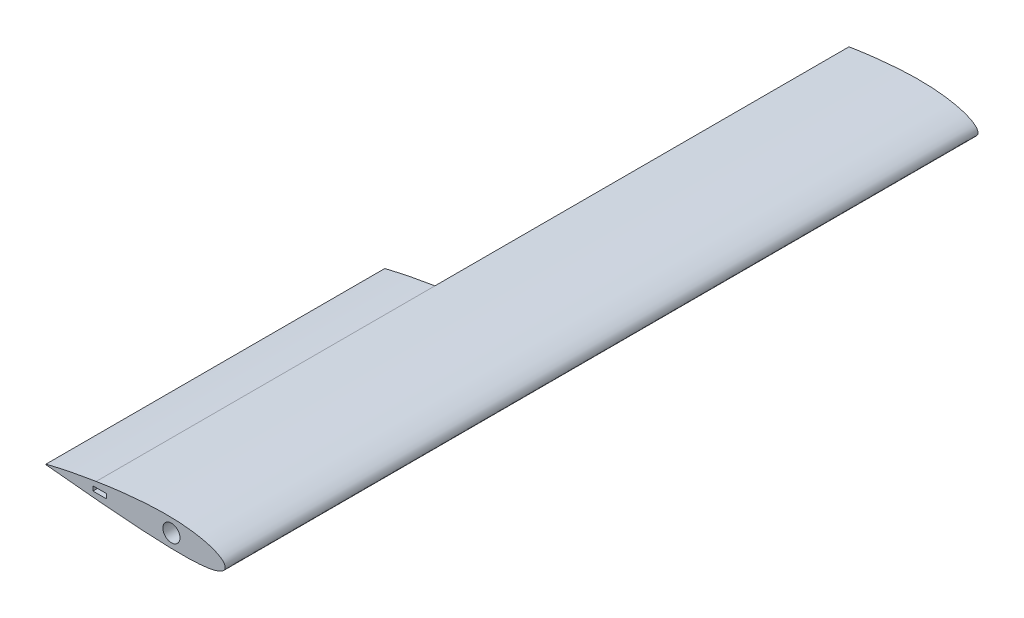
SolidWorks part; units mm, degrees
ref_plane "Front Plane" through (0, 0, 0) normal (0, 0, 1) x (1, 0, 0)
ref_plane "Top Plane" through (0, 0, 0) normal (0, 1, 0) x (1, 0, 0)
ref_plane "Right Plane" through (0, 0, 0) normal (1, 0, 0) x (0, 0, -1)
sketch "Sketch1" plane through (0, 0, 0) normal (0, 0, 1) x (1, 0, 0)
  line L0 (-191.9354, 15.416) -> (-191.9354, -7.6909)
  spline S0 degree 3 poles (-191.9354, 15.416) (-189.5243, 15.8004) (-183.84, 16.7066) (-174.7811, 18.0293) (-164.699, 19.4011) (-154.4132, 20.6737) (-143.9882, 21.8304) (-133.4887, 22.8492) (-122.9807, 23.7108) (-112.5154, 24.3961) (-102.1393, 24.8937) (-91.9165, 25.1258) (-81.9303, 25.09) (-72.2668, 24.7809) (-62.9911, 24.2008) (-54.1652, 23.3569) (-45.8482, 22.2615) (-38.0948, 20.9316) (-30.9554, 19.3888) (-24.475, 17.6581) (-18.6932, 15.7669) (-13.6432, 13.7442) (-9.3513, 11.6182) (-5.8361, 9.4143) (-3.1085, 7.1499) (-1.1753, 4.8279) (-0.0633, 2.4265) (0.145, -0.0146) (-0.5418, -2.3641) (-2.0929, -4.4987) (-4.4137, -6.4044) (-7.4763, -8.1169) (-11.2681, -9.647) (-15.7716, -10.9953) (-20.9621, -12.1581) (-26.8094, -13.1324) (-33.2789, -13.9168) (-40.3323, -14.5128) (-47.9288, -14.9252) (-56.0247, -15.1619) (-64.5743, -15.2345) (-73.5296, -15.1578) (-82.8407, -14.9489) (-92.4558, -14.628) (-102.3403, -14.213) (-112.4533, -13.7319) (-122.7326, -13.1417) (-133.0976, -12.467) (-143.4707, -11.7255) (-153.7893, -10.9348) (-163.9906, -10.111) (-174.0119, -9.2678) (-183.3072, -8.4625) (-189.2543, -7.9307) (-191.9354, -7.6909) knots 0 0 0 0 0.018424 0.043434 0.06908 0.095203 0.12164 0.148227 0.1748 0.201195 0.227364 0.253182 0.278347 0.30271 0.326128 0.348467 0.3696 0.389416 0.407811 0.424699 0.440008 0.453688 0.465715 0.476104 0.484928 0.49236 0.49873 0.504587 0.510443 0.516804 0.524199 0.532941 0.543186 0.554996 0.568376 0.583299 0.599709 0.617539 0.636704 0.657109 0.678651 0.701217 0.724685 0.748928 0.773811 0.799338 0.825326 0.851504 0.877716 0.9038 0.929596 0.954944 0.979688 1 1 1 1
extrude "Boss-Extrude1" add sketch "Sketch1" against normal blind 1120
sketch "Sketch2" plane through (0, 0, 0) normal (0, 0, 1) x (1, 0, 0)
  line L0 (-191.9354, 15.416) -> (-191.9354, -7.6909)
  line L1 (-266.577, 0.4257) -> (-266.577, -0.4189)
  spline S0 degree 3 poles (-191.9354, 15.416) (-192.6941, 15.2972) (-196.5004, 14.701) (-203.198, 13.5621) (-211.8684, 12.0329) (-220.0466, 10.5101) (-227.685, 9.0244) (-234.7376, 7.5953) (-241.1628, 6.245) (-246.9227, 4.9942) (-251.9835, 3.8631) (-256.316, 2.8703) (-259.895, 2.0327) (-262.7001, 1.365) (-264.7152, 0.8792) (-265.9195, 0.5864) (-266.4509, 0.4566) (-266.577, 0.4257) knots 0 0 0 0 0.030252 0.151774 0.267626 0.37709 0.479485 0.574175 0.66057 0.73813 0.806369 0.864859 0.913229 0.951173 0.978451 0.994887 1 1 1 1
  spline S1 degree 3 poles (-191.9354, -7.6909) (-192.4201, -7.6479) (-195.9505, -7.3341) (-202.3859, -6.745) (-211.0842, -5.9402) (-219.3093, -5.1646) (-227.0093, -4.427) (-234.1351, -3.7336) (-240.6411, -3.0907) (-246.4855, -2.5047) (-251.6304, -1.981) (-256.0423, -1.5274) (-259.6922, -1.1436) (-262.5569, -0.8499) (-264.6155, -0.6129) (-265.8584, -0.5128) (-266.419, -0.4184) (-266.5677, -0.4189) (-266.577, -0.4189) knots 0 0 0 0 0.019463 0.141781 0.258505 0.3689 0.472262 0.567931 0.655294 0.733785 0.802892 0.862162 0.911205 0.949694 0.977373 0.994054 0.999628 1 1 1 1
extrude "Boss-Extrude2" add sketch "Sketch2" against normal blind 504
sketch "Sketch3" plane through (0, 0, 0) normal (0, 0, 1) x (1, 0, 0)
  circle A0 centre (-79.973, 4.998) radius 12.7
extrude "Cut-Extrude1" cut sketch "Sketch3" against normal blind 801
ref_plane "Plane1" through (0, 0, -376.7) normal (0, 0, 1) x (1, 0, 0)
sketch "Sketch4" plane through (0, 0, -376.7) normal (0, 0, 1) x (1, 0, 0)
  line L0 (-95.973, -16.001) -> (-63.973, -16.001)
  line L1 (-63.973, -16.001) -> (-63.973, 20.698)
  line L2 (-63.973, 20.698) -> (-95.973, 20.698)
  line L3 (-95.973, 20.698) -> (-95.973, -16.001)
extrude "Cut-Extrude2" cut sketch "Sketch4" along normal blind 46
ref_plane "Plane2" through (0, 0, -376.7) normal (0, 0, 1) x (1, 0, 0)
sketch "Sketch5" plane through (0, 0, -376.7) normal (0, 0, 1) x (1, 0, 0)
  line L0 (-243.2616, -7.779) -> (-183.2616, -7.779)
  line L1 (-183.2616, -7.779) -> (-183.2616, 4.221)
  line L2 (-183.2616, 4.221) -> (-243.2616, 4.221)
  line L3 (-243.2616, 4.221) -> (-243.2616, -7.779)
extrude "Cut-Extrude3" cut sketch "Sketch5" along normal blind 46
ref_plane "Plane3" through (0, 0, -598.5) normal (0, 0, 1) x (1, 0, 0)
sketch "Sketch6" plane through (0, 0, -598.5) normal (0, 0, 1) x (1, 0, 0)
  line L0 (-173.617, -14.504) -> (-119.617, -14.504)
  line L1 (-119.617, -14.504) -> (-119.617, 14.596)
  line L2 (-119.617, 14.596) -> (-173.617, 14.596)
  line L3 (-173.617, 14.596) -> (-173.617, -14.504)
extrude "Cut-Extrude4" cut sketch "Sketch6" along normal blind 64
ref_plane "Plane4" through (0, 0, -25.5) normal (0, 0, 1) x (1, 0, 0)
sketch "Sketch7" plane through (0, 0, -25.5) normal (0, 0, 1) x (1, 0, 0)
  line L0 (-196.804, 0.599) -> (-176.404, 0.599)
  line L1 (-176.404, 0.599) -> (-176.404, 7.399)
  line L2 (-176.404, 7.399) -> (-196.804, 7.399)
  line L3 (-196.804, 7.399) -> (-196.804, 0.599)
extrude "Cut-Extrude5" cut sketch "Sketch7" along normal blind 26
ref_plane "Plane5" through (0, 0, -930) normal (0, 0, 1) x (1, 0, 0)
sketch "Sketch8" plane through (0, 0, -930) normal (0, 0, 1) x (1, 0, 0)
  line L0 (-60, -16.17) -> (-40, -16.17)
  line L1 (-40, -16.17) -> (-40, -12.17)
  line L2 (-40, -12.17) -> (-60, -12.17)
  line L3 (-60, -12.17) -> (-60, -16.17)
extrude "Cut-Extrude6" cut sketch "Sketch8" along normal blind 20
